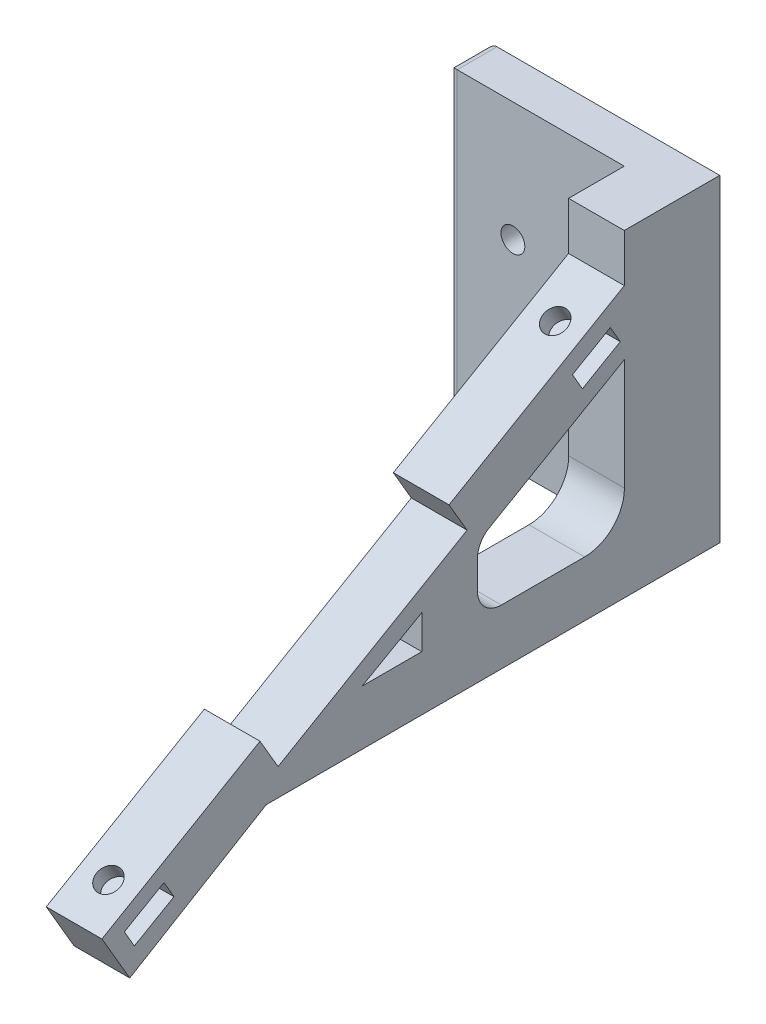
SolidWorks part; units mm, degrees
ref_plane "Front Plane" through (0, 0, 0) normal (0, 0, 1) x (1, 0, 0)
ref_plane "Top Plane" through (0, 0, 0) normal (0, 1, 0) x (1, 0, 0)
ref_plane "Right Plane" through (0, 0, 0) normal (1, 0, 0) x (0, 0, -1)
sketch "Sketch1" plane through (0, 0, 0) normal (1, 0, 0) x (0, 0, -1)
  line L0 (-21.7856, -17.3779) -> (35.2144, -17.3779)
  line L5 (35.2144, -17.3779) -> (35.2144, 22.6221)
  line L6 (35.2144, 22.6221) -> (23.2144, 22.6221)
  line L7 (23.2144, 22.6221) -> (23.2144, 16.6221)
  line L8 (1.1877, 3.774) -> (23.2144, 16.6221)
  line L9 (1.1877, 3.774) -> (3.455, -0.1131)
  line L10 (3.455, -0.1131) -> (-20.2993, -13.9689)
  line L11 (-20.2993, -13.9689) -> (-22.5666, -10.0818)
  line L12 (-22.5666, -10.0818) -> (-42.4338, -21.6704)
  line L13 (-42.4338, -21.6704) -> (-38.9371, -27.6651)
  line L14 (-38.9371, -27.6651) -> (-21.7856, -17.3779)
  line L15 (23.2341, 8.5696) -> (23.2341, -10.4179)
  line L19 (-39.6139, -22.3046) -> (-34.6345, -19.4291)
  line L20 (-34.6345, -19.4291) -> (-33.3843, -21.5941)
  line L21 (-33.3843, -21.5941) -> (-38.3637, -24.4695)
  line L22 (-38.3637, -24.4695) -> (-39.6139, -22.3046)
  line L23 (-9.7355, -10.4979) -> (-2.2353, -10.4979)
  line L24 (-2.2353, -10.4979) -> (-2.2353, -6.2484)
  line L25 (-2.2353, -6.2484) -> (-9.7355, -10.4979)
  line L26 (16.6994, 10.1829) -> (17.9518, 8.0192)
  line L27 (17.9518, 8.0192) -> (22.7119, 10.7746)
  line L28 (22.7119, 10.7746) -> (21.4594, 12.9383)
  line L29 (21.4594, 12.9383) -> (16.6994, 10.1829)
  line L31 (4.7647, -1.3999) -> (6.0116, -1.3999)
  line L32 (4.7647, -1.3999) -> (4.7647, -10.4179)
  line L33 (4.7647, -10.4179) -> (23.2341, -10.4179)
  line L36 (6.0116, -1.3999) -> (23.2341, 8.5696)
  dimension "D1" = 57
  dimension "D2" = 40
  dimension "D3" = 12
  dimension "D4" = 25.5
  dimension "D5" = 6
  dimension "D6" = 27.5
  dimension "D7" = 4.5
  dimension "D8" = 4.5
  dimension "D9" = 23
  dimension "D10" = 6.94
  dimension "D11" = 20
  dimension "D12" = 5.75
  dimension "D13" = 2.5
  dimension "D14" = 0.25
  dimension "D15" = 6.88
  dimension "D16" = 6.96
  dimension "D17" = 7
  dimension "D18" = 0.72
  dimension "D19" = 0.19
  dimension "D20" = 2.17
extrude "Boss-Extrude1" add sketch "Sketch1" against normal blind 7
fillet "Fillet1" radius 3 2 edges at (-3.5, -10.4179, -4.7647) (-3.5, -1.3999, -4.7647)
fillet "Fillet2" radius 5 1 edges at (-3.5, -10.4179, -23.2341)
sketch "Sketch2" plane through (-7, 0, 0) normal (-1, 0, 0) x (0, 0, 1)
  line L0 (21.7856, -17.3779) -> (-35.2144, -17.3779) construction
  line L1 (-35.2144, 22.6221) -> (-30.2144, 22.6221)
  line L2 (-35.2144, 22.6221) -> (-35.2144, -17.3779)
  line L3 (-35.2144, -17.3779) -> (-30.2144, -17.3779)
  line L4 (-30.2144, 22.6221) -> (-30.2144, -17.3779)
  dimension "D1" = 5
extrude "Boss-Extrude2" add sketch "Sketch2" along normal blind 22
sketch "Sketch4" plane through (0, 2.299, 1.341) normal (0, 0.8638, 0.5038) x (1, 0, 0)
  line L0 (0, 28.4274) -> (0, 2.9274) construction
  line L1 (-7, 28.4274) -> (0, 28.4274) construction
  line L2 (-7, -47.5726) -> (0, -47.5726) construction
  circle A0 centre (-3.5, 22.4274) radius 1.5
  circle A1 centre (-3.5, -42.5726) radius 1.5
  dimension "D1" = 3.5
  dimension "D2" = 6
  dimension "D3" = 5
extrude "Cut-Extrude1" cut sketch "Sketch4" against normal blind 3
sketch "Sketch5" plane through (0, 0, -30.2144) normal (0, 0, 1) x (1, 0, 0)
  line L0 (-29, -17.3779) -> (-29, 22.6221) construction
  line L1 (-29, -17.3779) -> (-7, -17.3779) construction
  circle A0 centre (-21, 7.6221) radius 1.5
  circle A1 centre (-21, -12.3779) radius 1.5
  dimension "D1" = 20
  dimension "D2" = 8
  dimension "D3" = 5
extrude "Cut-Extrude2" cut sketch "Sketch5" against normal blind 5
fillet "Fillet3" radius 1 4 edges at (-29, 2.6221, -30.2144) (-29, 2.6221, -35.2144) (-29, -17.3779, -32.7144) (-29, 22.6221, -32.7144)
